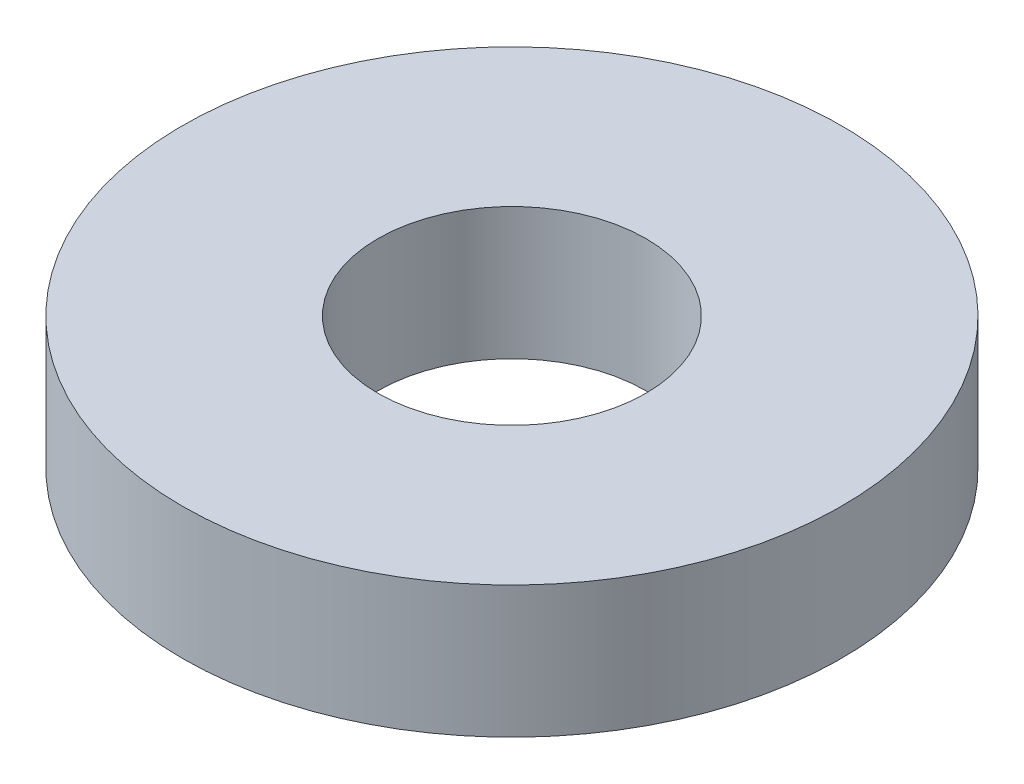
SolidWorks part; units mm, degrees
ref_plane "Front Plane" through (0, 0, 0) normal (0, 0, 1) x (1, 0, 0)
ref_plane "Top Plane" through (0, 0, 0) normal (0, 1, 0) x (1, 0, 0)
ref_plane "Right Plane" through (0, 0, 0) normal (1, 0, 0) x (0, 0, -1)
sketch "Sketch1" plane through (0, 0, 0) normal (0, 1, 0) x (1, 0, 0)
  circle A0 centre (0, 0) radius 7.5
  circle A1 centre (0, 0) radius 3.05
  dimension "D1" = 15
  dimension "D2" = 6.1
extrude "Boss-Extrude1" add sketch "Sketch1" along normal blind 3
ref_axis "Axis1" through (0, 0, -8.25) along (0, 0, 1)
sketch "Sketch3" plane through (0, 0, 0) normal (1, 0, 0) x (0, 0, -1)
  line L1 (4.35, 0) -> (5.75, 0)
  arc A0 (4.35, 0) -> (5.75, 0) centre (5.05, 0) ccw
  dimension "D1" = 2
  dimension "D2" = 1.4
revolve "Revolve2" add sketch "Sketch3" angle 360 about axis through (0, 0, -8.25) along (0, 0, 1)
ref_axis "Axis2" through (0, -0.885, 0) along (0, 1, 0)
pattern_circular "CirPattern1" count 10 over 360 about axis through (0, -0.885, 0) along (0, 1, 0) of "Revolve2"
